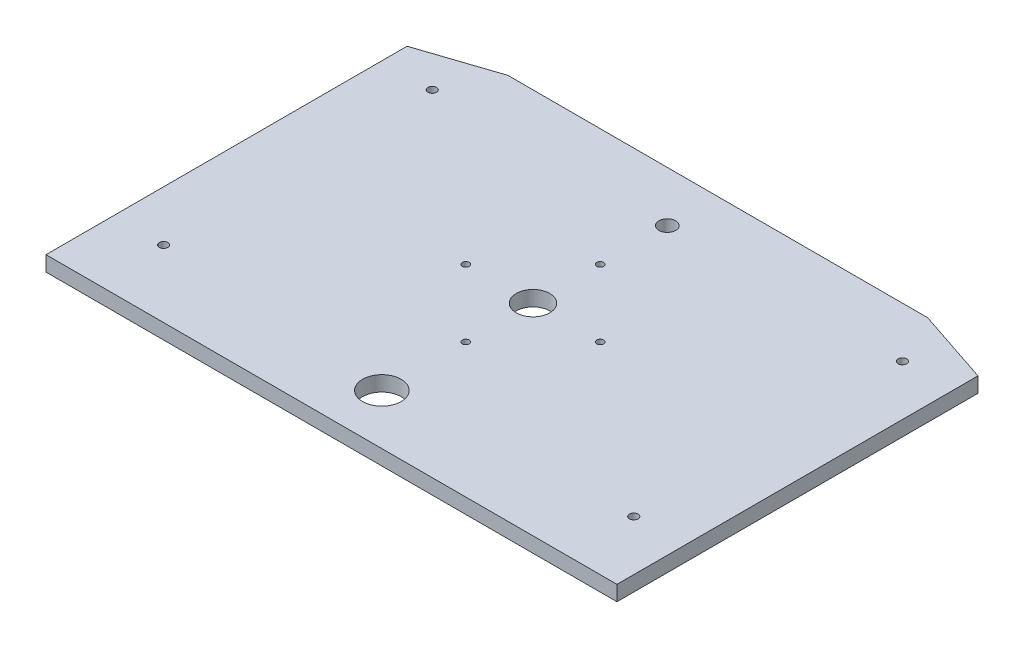
SolidWorks part; units mm, degrees
ref_plane "Plan de face" through (0, 0, 0) normal (0, 0, 1) x (1, 0, 0)
ref_plane "Plan de dessus" through (0, 0, 0) normal (0, 1, 0) x (1, 0, 0)
ref_plane "Plan de droite" through (0, 0, 0) normal (1, 0, 0) x (0, 0, -1)
sketch "Esquisse3" plane through (0, 0, 0) normal (0, 1, 0) x (1, 0, 0)
  line L0 (-281.7629, 0) -> (308.2067, 0) construction
  line L1 (0, 166.4902) -> (0, -269.1166) construction
  line L4 (-160, -46) -> (-160, 46) construction
  line L5 (-156, 50) -> (-149, 50) construction
  line L6 (-145, 46) -> (-145, -46) construction
  line L7 (-105, 0) -> (-105, 31) construction
  line L8 (-101, 35) -> (-74, 35) construction
  line L9 (-70, 31) -> (-70, -31) construction
  line L11 (-105, 0) -> (-105, -31) construction
  line L12 (-101, -35) -> (-74, -35) construction
  line L13 (-156, -50) -> (-149, -50) construction
  line L17 (156, 50) -> (149, 50) construction
  line L18 (156, -50) -> (149, -50) construction
  line L19 (145, 46) -> (145, -46) construction
  line L20 (160, -46) -> (160, 46) construction
  line L21 (105, 0) -> (105, 31) construction
  line L22 (101, -35) -> (74, -35) construction
  line L23 (105, 0) -> (105, -31) construction
  line L24 (70, 31) -> (70, -31) construction
  line L25 (101, 35) -> (74, 35) construction
  line L26 (125, 110) -> (-125, 110)
  line L34 (-170, 95) -> (-125, 110)
  line L35 (170, 95) -> (125, 110)
  line L38 (-170, 95) -> (-170, 0)
  line L39 (-170, 0) -> (-170, -120)
  line L40 (170, -120) -> (170, 0)
  line L41 (170, 0) -> (170, 95)
  line L43 (-170, -120) -> (-150, -140)
  line L44 (150, -140) -> (170, -120)
  line L45 (-150, -140) -> (-120, -140)
  line L46 (-120, -140) -> (-120, -55) construction
  line L47 (-120, -55) -> (120, -55) construction
  line L48 (120, -55) -> (120, -140) construction
  line L49 (120, -140) -> (150, -140)
  line L50 (-170, 95) -> (170, 95) construction
  line L51 (-170, 0) -> (-220, 0) construction
  line L52 (-220, 0) -> (-170, 95) construction
  line L53 (-220, 0) -> (-170, -120) construction
  line L54 (-130, -140) -> (-130, -220) construction
  line L55 (-130, -220) -> (130, -220) construction
  line L56 (130, -140) -> (130, -220) construction
  line L57 (-170, -120) -> (-130, -220) construction
  line L58 (-120, -140) -> (120, -140)
  line L59 (-170, -120) -> (170, -120)
  arc A0 (-149, 50) -> (-145, 46) centre (-149, 46) cw construction
  arc A1 (-74, 35) -> (-70, 31) centre (-74, 31) cw construction
  arc A2 (-105, 31) -> (-101, 35) centre (-101, 31) cw construction
  arc A3 (-160, 46) -> (-156, 50) centre (-156, 46) cw construction
  arc A4 (-105, -31) -> (-101, -35) centre (-101, -31) ccw construction
  arc A5 (-74, -35) -> (-70, -31) centre (-74, -31) ccw construction
  arc A6 (-160, -46) -> (-156, -50) centre (-156, -46) ccw construction
  arc A7 (-149, -50) -> (-145, -46) centre (-149, -46) ccw construction
  arc A8 (149, 50) -> (145, 46) centre (149, 46) ccw construction
  arc A9 (160, 46) -> (156, 50) centre (156, 46) ccw construction
  arc A10 (149, -50) -> (145, -46) centre (149, -46) cw construction
  arc A11 (160, -46) -> (156, -50) centre (156, -46) cw construction
  arc A12 (74, -35) -> (70, -31) centre (74, -31) cw construction
  arc A13 (105, -31) -> (101, -35) centre (101, -31) cw construction
  arc A14 (105, 31) -> (101, 35) centre (101, 31) ccw construction
  arc A15 (74, 35) -> (70, 31) centre (74, 31) ccw construction
  circle A16 centre (-140, 80) radius 2.55
  circle A17 centre (-140, -80) radius 2.55
  circle A18 centre (140, -80) radius 2.55
  circle A19 centre (140, 80) radius 2.55
  point P6 (-170, 110)
  point P16 (-105, 15.5)
  point P19 (-145, 50)
  point P22 (-70, 35)
  point P25 (-105, 35)
  point P28 (-160, 50)
  point P32 (-70, 0)
  point P37 (-105, -35)
  point P38 (-70, -35)
  point P40 (-145, 0)
  point P41 (-160, 0)
  point P45 (-160, -50)
  point P46 (-145, -50)
  point P47 (0, 110)
  point P48 (-170, 0)
  point P51 (0, -110)
  point P64 (145, -50)
  point P65 (160, -50)
  point P75 (70, -35)
  point P76 (105, -35)
  point P81 (105, 35)
  point P82 (70, 35)
  point P83 (0, -269.1166)
  point P85 (0, 110)
  point P94 (-170, 0)
  point P97 (170, 0)
  point P100 (0, -130)
  dimension "D7" = 4
  dimension "D10" = 5.1
  dimension "D2" = 250
  dimension "D3" = 35
  dimension "D4" = 15
  dimension "D5" = 70
  dimension "D6" = 40
  dimension "D14" = 30
  dimension "D13" = 110
  dimension "D8" = 35
  dimension "D9" = 50
  dimension "D11" = 240
  dimension "D12" = 340
  dimension "D15" = 120
  dimension "D16" = 95
  dimension "D17" = 140
  dimension "D18" = 80
  dimension "D19" = 85
  dimension "D20" = 140
  dimension "D21" = 125
  dimension "D22" = 28.2843
  dimension "D23" = 47.4342
  dimension "D24" = 120
  dimension "D25" = 50
  dimension "D26" = 130
  dimension "D27" = 107.3546
  dimension "D28" = 80
  dimension "D29" = 10
  dimension "D30" = 107.7033
  dimension "D31" = 130
  dimension "D32" = 40
extrude "structure" add sketch "Esquisse3" against normal blind 9 contours L39 L59 L40 L41 L35 L26 L34 L38 A17 A16 A18 A19 region at (0, 0, 5.964)
sketch "Esquisse4" plane through (0, 0, 0) normal (0, 1, 0) x (1, 0, 0)
  line L0 (0, 110) -> (0, -140) construction
  line L1 (125, 110) -> (-125, 110) construction
  line L2 (-150, -140) -> (150, -140) construction
  line L3 (-170, 0) -> (170, 0) construction
  line L4 (-170, 95) -> (-170, -120) construction
  line L5 (170, -120) -> (170, 95) construction
  circle A0 centre (0, 0) radius 10
  circle A1 centre (0, -90) radius 11.5
  circle A2 centre (0, 0) radius 40 construction
  circle A3 centre (0, 40) radius 2.05
  circle A4 centre (40, 0) radius 2.05
  circle A5 centre (0, -40) radius 2.05
  circle A6 centre (-40, 0) radius 2.05
  circle A7 centre (0, 0) radius 30.8 construction
  circle A8 centre (0, 80) radius 5
  point P29 (0, 0)
  point P30 (0, -140)
  dimension "D1" = 23
  dimension "D3" = 20
  dimension "D4" = 4.1
  dimension "D6" = 80
  dimension "D7" = 61.6
  dimension "D8" = 10
  dimension "D2" = 90
  dimension "D9" = 80
  dimension "D5" = 4
extrude "Enlèv. mat.-Extru.1" cut sketch "Esquisse4" against normal blind 10
